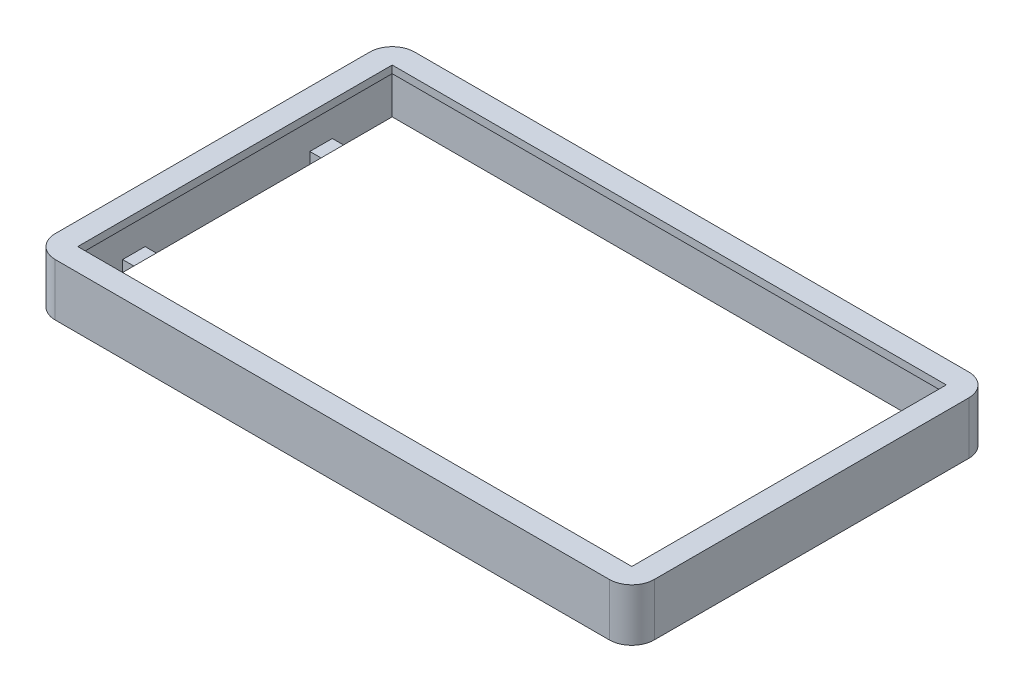
SolidWorks part; units mm, degrees
ref_plane "Front Plane" through (0, 0, 0) normal (0, 0, 1) x (1, 0, 0)
ref_plane "Top Plane" through (0, 0, 0) normal (0, 1, 0) x (1, 0, 0)
ref_plane "Right Plane" through (0, 0, 0) normal (1, 0, 0) x (0, 0, -1)
sketch "Sketch1" plane through (0, 0, 0) normal (0, 1, 0) x (1, 0, 0)
  line L0 (-40, 24) -> (-40, -24)
  line L1 (-38, 22) -> (38, 22)
  line L2 (-38, 22) -> (-38, -22)
  line L3 (-38, -22) -> (38, -22)
  line L4 (38, 22) -> (38, -22)
  line L5 (-38, 22) -> (38, -22) construction
  line L6 (-38, -22) -> (38, 22) construction
  line L7 (-40, -24) -> (40, -24)
  line L8 (40, 24) -> (40, -24)
  line L9 (-40, 24) -> (40, 24)
  point P0 (0, 0)
  dimension "D1" = 44
  dimension "D2" = 76
  dimension "D3" = 2
extrude "Boss-Extrude1" add sketch "Sketch1" along normal blind 6
sketch "Sketch2" plane through (0, 6, 0) normal (0, 1, 0) x (1, 0, 0)
  line L0 (37, 21) -> (-37, 21)
  line L1 (-37, 21) -> (-37, -21)
  line L2 (-37, -21) -> (37, -21)
  line L3 (37, -21) -> (37, 21)
  line L4 (40, 24) -> (-40, 24)
  line L5 (-40, 24) -> (-40, -24)
  line L6 (-40, -24) -> (40, -24)
  line L7 (40, -24) -> (40, 24)
  line L8 (40, 24) -> (-40, 24)
  line L9 (-40, 24) -> (-40, -24)
  line L10 (-40, -24) -> (40, -24)
  line L11 (40, -24) -> (40, 24)
  dimension "D1" = 0
  dimension "D2" = 3
extrude "Boss-Extrude2" add sketch "Sketch2" along normal blind 1
fillet "Fillet1" radius 3 4 edges at (40, 3.5, -24) (40, 3.5, 24) (-40, 3.5, 24) (-40, 3.5, -24)
sketch "Sketch3" plane through (0, 0, 0) normal (0, -1, 0) x (1, 0, 0)
  line L1 (0, 0) -> (0, 11.4398) construction
  line L2 (-38, 22) -> (38, 22)
  line L3 (-38, 22) -> (-38, -22)
  line L4 (-37, -24) -> (37, -24)
  line L5 (40, -21) -> (40, 21)
  line L6 (37, 24) -> (-37, 24)
  line L7 (-40, 21) -> (-40, -21)
  line L8 (-37, -24) -> (37, -24)
  line L9 (40, -21) -> (40, 21)
  line L10 (37, 24) -> (-37, 24)
  line L11 (-40, 21) -> (-40, -21)
  line L12 (-38, -22) -> (38, -22)
  line L13 (38, 22) -> (38, -22)
  line L14 (0, 0) -> (10.3769, 0) construction
  line L15 (-38, -11) -> (-36.5, -11)
  line L16 (-38, 14) -> (-36.5, 14)
  line L17 (-38, 14) -> (-38, 11)
  line L18 (-38, 11) -> (-36.5, 11)
  line L19 (-36.5, 14) -> (-36.5, 11)
  line L20 (-36.5, -14) -> (-36.5, -11)
  line L21 (-38, -14) -> (-36.5, -14)
  line L22 (-38, -14) -> (-38, -11)
  line L31 (-26, 22) -> (-21, 22)
  line L32 (-26, 22) -> (-26, 20.5)
  line L33 (-26, 20.5) -> (-21, 20.5)
  line L34 (-21, 22) -> (-21, 20.5)
  line L35 (26, 20.5) -> (21, 20.5)
  line L36 (21, 22) -> (21, 20.5)
  line L37 (26, 22) -> (21, 22)
  line L38 (26, 22) -> (26, 20.5)
  arc A4 (37, -24) -> (40, -21) centre (37, -21) ccw
  arc A5 (40, 21) -> (37, 24) centre (37, 21) ccw
  arc A6 (-37, 24) -> (-40, 21) centre (-37, 21) ccw
  arc A7 (-40, -21) -> (-37, -24) centre (-37, -21) ccw
  arc A8 (37, -24) -> (40, -21) centre (37, -21) ccw
  arc A9 (40, 21) -> (37, 24) centre (37, 21) ccw
  arc A10 (-37, 24) -> (-40, 21) centre (-37, 21) ccw
  arc A11 (-40, -21) -> (-37, -24) centre (-37, -21) ccw
  line M13 (-37, -24) -> (37, -24)
  arc M14 (37, -24) -> (40, -21) centre (37, -21) ccw
  line M15 (40, -21) -> (40, 21)
  arc M16 (40, 21) -> (37, 24) centre (37, 21) ccw
  line M17 (37, 24) -> (-37, 24)
  arc M18 (-37, 24) -> (-40, 21) centre (-37, 21) ccw
  line M19 (-40, 21) -> (-40, -21)
  arc M20 (-40, -21) -> (-37, -24) centre (-37, -21) ccw
  line M21 (-38, 22) -> (38, 22)
  line M22 (38, 22) -> (38, -22)
  line M23 (38, -22) -> (-38, -22)
  line M24 (-38, -22) -> (-38, 22)
  dimension "D2" = 1.5
  dimension "D3" = 3
  dimension "D4" = 28
  dimension "D5" = 1.5
  dimension "D6" = 52
  dimension "D7" = 5
  dimension "D1" = 0
extrude "Boss-Extrude3" add sketch "Sketch3" against normal blind 1.5 contours M20 M13 M14 M15 M16 M17 M18 M19 M24 M21 M22 M23 | L34 L32 L33 M21 | L19 L16 L18 M24 | L21 L20 L15 M24 | L38 L36 L35 M21 | L8 A8 L9 A9 L10 A10 L11 A11 | L3 L2 L13 L12 region at (-23.5, 0, 21.25) region at (-37.25, 0, 12.5) region at (23.5, 0, 21.25) region at (-37.25, 0, -12.5) region at (-38.4616, 0, -22.4616)
chamfer "Chamfer2" distance 1.5 angle 45 4 edges at (23.5, 0, 20.5) (-23.5, 0, 20.5) (-36.5, 0, -12.5) (-36.5, 0, 12.5)
